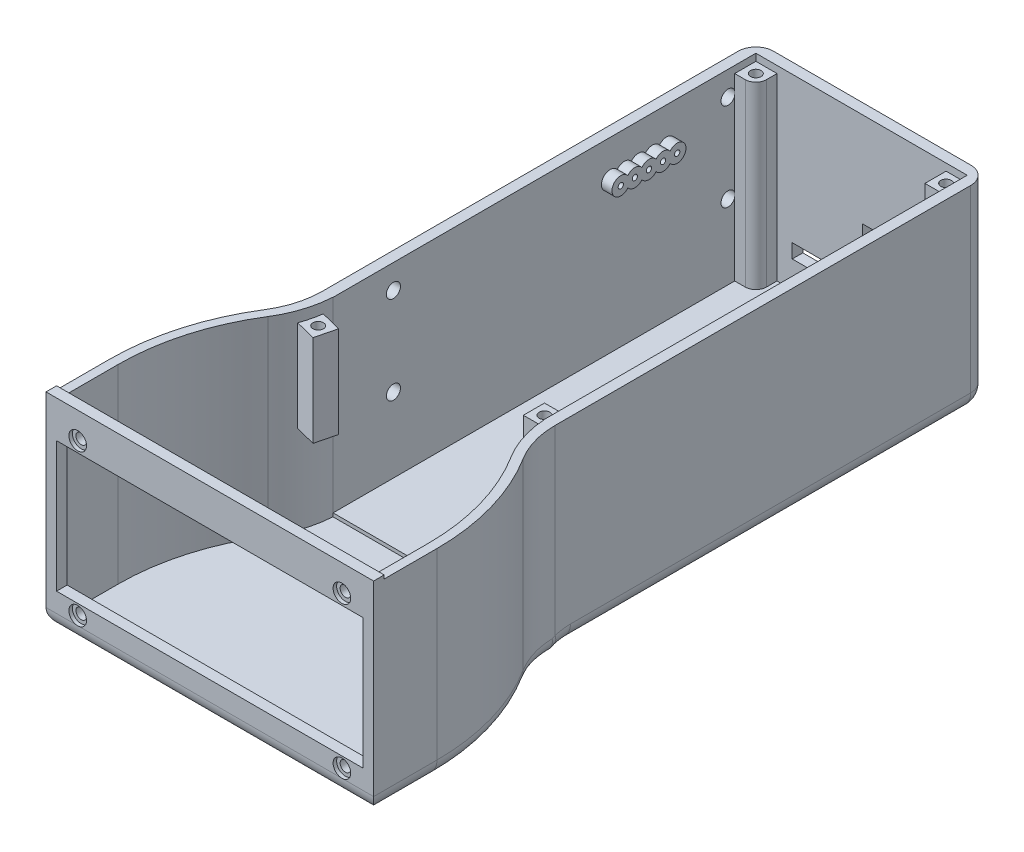
SolidWorks part; units mm, degrees
ref_plane "Front Plane" through (0, 0, 0) normal (0, 0, 1) x (1, 0, 0)
ref_plane "Top Plane" through (0, 0, 0) normal (0, 1, 0) x (1, 0, 0)
ref_plane "Right Plane" through (0, 0, 0) normal (1, 0, 0) x (0, 0, -1)
sketch "Sketch2" plane through (0, 0, -185.0054) normal (0, 0, -1) x (-1, 0, 0)
  line L0 (-30, -25) -> (0, 0) construction
  line L1 (-30, 25) -> (30, 25) construction
  line L2 (-30, 25) -> (-30, -25)
  line L3 (-30, -25) -> (30, -25)
  line L4 (30, 25) -> (30, -25)
  line L5 (0, 0) -> (30, 25) construction
  line L6 (-30, 25) -> (0, 0) construction
  line L7 (0, 0) -> (30, -25) construction
  line L8 (-33, 28) -> (-33, -28)
  line L9 (-33, -28) -> (33, -28)
  line L10 (33, 28) -> (33, -28)
  line L11 (-33, 28) -> (-30, 28)
  line L12 (30, 25) -> (30, 28)
  line L13 (-30, 25) -> (-30, 28)
  line L14 (-30, 28) -> (30, 28) construction
  line L15 (30, 28) -> (33, 28)
  line L16 (-33, 28) -> (33, 28) construction
  dimension "D1" = 60
  dimension "D2" = 50
  dimension "D3" = 3
extrude "Boss-Extrude1" add sketch "Sketch2" against normal blind 120
sketch "Sketch3" plane through (0, -25, 0) normal (0, 1, 0) x (1, 0, 0)
  line L1 (-33, 185.0054) -> (33, 185.0054)
  line L2 (-33, 185.0054) -> (-33, 188.0054)
  line L3 (-33, 188.0054) -> (33, 188.0054)
  line L4 (33, 185.0054) -> (33, 188.0054)
  dimension "D1" = 3
extrude "Boss-Extrude3" add sketch "Sketch3" along normal blind 53 and the other way blind 3
sketch "Sketch4" plane through (0, 0, -188.0054) normal (0, 0, -1) x (-1, 0, 0)
  line L0 (-13.3183, 1.1961) -> (-13.3183, -6.8039)
  line L1 (-12.8183, 0.6961) -> (-0.8183, 0.6961) construction
  line L2 (-12.8183, 0.6961) -> (-12.8183, -6.3039) construction
  line L3 (-12.8183, -6.3039) -> (-0.8183, -6.3039) construction
  line L4 (-0.8183, 0.6961) -> (-0.8183, -6.3039) construction
  line L5 (-13.3183, -6.8039) -> (-0.3183, -6.8039)
  line L6 (-0.3183, 1.1961) -> (-0.3183, -6.8039)
  line L7 (-13.3183, 1.1961) -> (-0.3183, 1.1961)
  line L8 (10.6709, -13.4176) -> (10.6709, -17.4176)
  line L9 (11.1709, -13.9176) -> (19.1709, -13.9176) construction
  line L10 (11.1709, -13.9176) -> (11.1709, -16.9176) construction
  line L11 (11.1709, -16.9176) -> (19.1709, -16.9176) construction
  line L12 (19.1709, -13.9176) -> (19.1709, -16.9176) construction
  line L13 (10.6709, -17.4176) -> (19.6709, -17.4176)
  line L14 (19.6709, -13.4176) -> (19.6709, -17.4176)
  line L15 (10.6709, -13.4176) -> (19.6709, -13.4176)
  line L36 (-12.0343, -12.8639) -> (-2.0343, -20.8639) construction
  line L38 (-12.0343, -19.8639) -> (-2.0343, -19.8639)
  line L39 (-12.0343, -19.8639) -> (-12.0343, -13.8639)
  line L40 (-12.0343, -13.8639) -> (-2.0343, -13.8639)
  line L41 (-2.0343, -19.8639) -> (-2.0343, -13.8639)
  line L42 (-12.0343, -19.8639) -> (-2.0343, -13.8639) construction
  line L43 (-12.0343, -13.8639) -> (-2.0343, -19.8639) construction
  circle A12 centre (1.4657, -16.8639) radius 1.5 construction
  circle A13 centre (-15.5343, -16.8639) radius 1.5 construction
  circle A14 centre (1.4657, -16.8639) radius 1.5
  circle A15 centre (-15.5343, -16.8639) radius 1.5
  arc A16 (-3.0343, -21.8639) -> (-2.0343, -20.8639) centre (-3.0343, -20.8639) ccw construction
  point P31 (-7.0343, -16.8639)
  dimension "D3" = 6
  dimension "D4" = 10
  dimension "D1" = 0.5
  dimension "D2" = 0.5
extrude "Cut-Extrude1" cut sketch "Sketch4" against normal up to next
sketch "Sketch5" plane through (-33, 0, 0) normal (-1, 0, 0) x (0, 0, 1)
  line L0 (-143.2154, 18.1363) -> (-144.1154, 18.1363) construction
  line L1 (-144.1154, 18.1363) -> (-144.1154, 17.0363) construction
  line L2 (-144.1154, 17.0363) -> (-143.2154, 17.0363) construction
  line L3 (-143.2154, 17.0363) -> (-143.2154, 18.1363) construction
  line L4 (-147.2154, 18.1363) -> (-148.1154, 18.1363) construction
  line L5 (-148.1154, 18.1363) -> (-148.1154, 17.0363) construction
  line L6 (-148.1154, 17.0363) -> (-147.2154, 17.0363) construction
  line L7 (-147.2154, 17.0363) -> (-147.2154, 18.1363) construction
  line L8 (-151.2154, 18.1363) -> (-152.1154, 18.1363) construction
  line L9 (-152.1154, 18.1363) -> (-152.1154, 17.0363) construction
  line L10 (-152.1154, 17.0363) -> (-151.2154, 17.0363) construction
  line L11 (-151.2154, 17.0363) -> (-151.2154, 18.1363) construction
  line L12 (-155.2154, 18.1363) -> (-156.1154, 18.1363) construction
  line L13 (-156.1154, 18.1363) -> (-156.1154, 17.0363) construction
  line L14 (-156.1154, 17.0363) -> (-155.2154, 17.0363) construction
  line L15 (-155.2154, 17.0363) -> (-155.2154, 18.1363) construction
  line L16 (-160.1154, 17.0363) -> (-159.2154, 17.0363) construction
  line L17 (-159.2154, 17.0363) -> (-159.2154, 18.1363) construction
  line L18 (-159.2154, 18.1363) -> (-160.1154, 18.1363) construction
  line L19 (-160.1154, 18.1363) -> (-160.1154, 17.0363) construction
  line L20 (-143.2154, 18.1363) -> (-144.1154, 18.1363) construction
  line L21 (-144.1154, 18.1363) -> (-144.1154, 17.0363) construction
  line L22 (-144.1154, 17.0363) -> (-143.2154, 17.0363) construction
  line L23 (-143.2154, 17.0363) -> (-143.2154, 18.1363) construction
  line L24 (-147.2154, 18.1363) -> (-148.1154, 18.1363) construction
  line L25 (-148.1154, 18.1363) -> (-148.1154, 17.0363) construction
  line L26 (-148.1154, 17.0363) -> (-147.2154, 17.0363) construction
  line L27 (-147.2154, 17.0363) -> (-147.2154, 18.1363) construction
  line L28 (-151.2154, 18.1363) -> (-152.1154, 18.1363) construction
  line L29 (-152.1154, 18.1363) -> (-152.1154, 17.0363) construction
  line L30 (-152.1154, 17.0363) -> (-151.2154, 17.0363) construction
  line L31 (-151.2154, 17.0363) -> (-151.2154, 18.1363) construction
  line L32 (-155.2154, 18.1363) -> (-156.1154, 18.1363) construction
  line L33 (-156.1154, 18.1363) -> (-156.1154, 17.0363) construction
  line L34 (-156.1154, 17.0363) -> (-155.2154, 17.0363) construction
  line L35 (-155.2154, 17.0363) -> (-155.2154, 18.1363) construction
  line L36 (-160.1154, 17.0363) -> (-159.2154, 17.0363) construction
  line L37 (-159.2154, 17.0363) -> (-159.2154, 18.1363) construction
  line L38 (-159.2154, 18.1363) -> (-160.1154, 18.1363) construction
  line L39 (-160.1154, 18.1363) -> (-160.1154, 17.0363) construction
  line L40 (-160.1154, 17.0363) -> (-159.2154, 18.1363) construction
  line L41 (-156.1154, 17.0363) -> (-155.2154, 18.1363) construction
  line L42 (-152.1154, 17.0363) -> (-151.2154, 18.1363) construction
  line L43 (-148.1154, 18.1363) -> (-147.2154, 17.0363) construction
  line L44 (-144.1154, 17.0363) -> (-143.2154, 18.1363) construction
  circle A0 centre (-82.1154, 21.1363) radius 1.5 construction
  circle A1 centre (-82.1154, -3.8637) radius 1.5 construction
  circle A2 centre (-177.1154, 21.1363) radius 1.5 construction
  circle A3 centre (-177.1154, -3.8637) radius 1.5 construction
  circle A4 centre (-82.1154, 21.1363) radius 1.5 construction
  circle A5 centre (-82.1154, -3.8637) radius 1.5 construction
  circle A6 centre (-177.1154, 21.1363) radius 1.5 construction
  circle A7 centre (-177.1154, -3.8637) radius 1.5 construction
  circle A8 centre (-177.1154, 21.1363) radius 2
  circle A9 centre (-177.1154, -3.8637) radius 2
  circle A10 centre (-82.1154, -3.8637) radius 2
  circle A11 centre (-82.1154, 21.1363) radius 2
  circle A12 centre (-159.6654, 17.5863) radius 0.75
  circle A13 centre (-155.6654, 17.5863) radius 0.75
  circle A14 centre (-151.6654, 17.5863) radius 0.75
  circle A15 centre (-147.6654, 17.5863) radius 0.75
  circle A16 centre (-143.6654, 17.5863) radius 0.75
  dimension "D1" = 0.5
  dimension "D2" = 1.5
  dimension "D3" = 1.5
  dimension "D4" = 1.5
  dimension "D5" = 1.5
  dimension "D6" = 1.5
extrude "Cut-Extrude2" cut sketch "Sketch5" against normal up to next
sketch "Sketch6" plane through (-33, 0, 0) normal (-1, 0, 0) x (0, 0, 1)
  arc A0 (-157.6654, 19.0863) -> (-157.6654, 16.0863) centre (-159.6654, 17.5863) ccw
  arc A1 (-157.6654, 16.0863) -> (-153.6654, 16.0863) centre (-155.6654, 17.5863) ccw
  arc A2 (-153.6654, 16.0863) -> (-149.6654, 16.0863) centre (-151.6654, 17.5863) ccw
  arc A3 (-149.6654, 16.0863) -> (-145.6654, 16.0863) centre (-147.6654, 17.5863) ccw
  arc A4 (-145.6654, 16.0863) -> (-145.6654, 19.0863) centre (-143.6654, 17.5863) ccw
  circle A5 centre (-159.6654, 17.5863) radius 0.75 construction
  circle A6 centre (-155.6654, 17.5863) radius 0.75 construction
  circle A7 centre (-151.6654, 17.5863) radius 0.75 construction
  circle A8 centre (-147.6654, 17.5863) radius 0.75 construction
  circle A9 centre (-143.6654, 17.5863) radius 0.75 construction
  circle A10 centre (-159.6654, 17.5863) radius 0.75
  circle A11 centre (-155.6654, 17.5863) radius 0.75
  circle A12 centre (-151.6654, 17.5863) radius 0.75
  circle A13 centre (-147.6654, 17.5863) radius 0.75
  circle A14 centre (-143.6654, 17.5863) radius 0.75
  arc A15 (-157.6654, 19.0863) -> (-157.6654, 16.0863) centre (-155.6654, 17.5863) ccw construction
  arc A16 (-157.6654, 16.0863) -> (-157.6654, 19.0863) centre (-159.6654, 17.5863) ccw construction
  arc A17 (-153.6654, 19.0863) -> (-153.6654, 16.0863) centre (-151.6654, 17.5863) ccw construction
  arc A18 (-153.6654, 16.0863) -> (-153.6654, 19.0863) centre (-155.6654, 17.5863) ccw construction
  arc A19 (-153.6654, 19.0863) -> (-157.6654, 19.0863) centre (-155.6654, 17.5863) ccw
  arc A20 (-149.6654, 19.0863) -> (-149.6654, 16.0863) centre (-147.6654, 17.5863) ccw construction
  arc A21 (-149.6654, 16.0863) -> (-149.6654, 19.0863) centre (-151.6654, 17.5863) ccw construction
  arc A22 (-149.6654, 19.0863) -> (-153.6654, 19.0863) centre (-151.6654, 17.5863) ccw
  arc A23 (-145.6654, 19.0863) -> (-145.6654, 16.0863) centre (-143.6654, 17.5863) ccw construction
  arc A24 (-145.6654, 16.0863) -> (-145.6654, 19.0863) centre (-147.6654, 17.5863) ccw construction
  arc A25 (-145.6654, 19.0863) -> (-149.6654, 19.0863) centre (-147.6654, 17.5863) ccw
  dimension "D1" = 5
  dimension "D2" = 5
  dimension "D3" = 5
  dimension "D4" = 5
  dimension "D5" = 5
extrude "Boss-Extrude4" add sketch "Sketch6" against normal blind 3 from surface starting at face at (-30, -3.8637, -179.1154)
sketch "Sketch7" plane through (0, 0, 0) normal (0, 0, 1) x (1, 0, 0)
  line L0 (-43, -18) -> (43, -18) construction
  line L1 (43, -18) -> (43, 18) construction
  line L2 (-43, 18) -> (43, 18) construction
  line L3 (-43, -18) -> (-43, 18) construction
  line L4 (-43, -18) -> (43, -18) construction
  line L5 (43, -18) -> (43, 18) construction
  line L6 (-43, 18) -> (43, 18) construction
  line L7 (-43, -18) -> (-43, 18) construction
  line L8 (-43.5, -18.5) -> (-43.5, 18.5)
  line L9 (-43.5, 18.5) -> (43.5, 18.5)
  line L10 (43.5, -18.5) -> (43.5, 18.5)
  line L11 (-43.5, -18.5) -> (43.5, -18.5)
  line L13 (46.5, -29) -> (-46.5, -29)
  line L14 (46.5, -29) -> (46.5, 29)
  line L15 (46.5, 29) -> (-46.5, 29)
  line L16 (-46.5, -29) -> (-46.5, 29)
  line L17 (46.5, -29) -> (-46.5, 29) construction
  line L18 (46.5, 29) -> (-46.5, -29) construction
  circle A0 centre (37.5, 21.5) radius 1.5 construction
  circle A1 centre (37.5, -21.5) radius 1.5 construction
  circle A2 centre (-37.5, -21.5) radius 1.5 construction
  circle A3 centre (-37.5, 21.5) radius 1.5 construction
  circle A4 centre (37.5, 21.5) radius 1.5
  circle A5 centre (37.5, -21.5) radius 1.5
  circle A6 centre (-37.5, -21.5) radius 1.5
  circle A7 centre (-37.5, 21.5) radius 1.5
  point P20 (0, 0)
  dimension "D2" = 3
  dimension "D3" = 7.5
  dimension "D1" = 0.5
extrude "Boss-Extrude5" add sketch "Sketch7" against normal blind 3 separate body
sketch "Sketch8" plane through (0, 0, 0) normal (0, 0, 1) x (1, 0, 0)
  circle A11 centre (-37.5, 21.5) radius 2.5
  circle A12 centre (37.5, 21.5) radius 2.5
  circle A13 centre (37.5, -21.5) radius 2.5
  circle A14 centre (-37.5, -21.5) radius 2.5
  point P0 (37.5, 21.5)
  point P1 (37.5, -21.5)
  point P2 (-37.5, -21.5)
  point P22 (-37.5, 21.5)
  dimension "D1" = 5
  dimension "D2" = 5
  dimension "D3" = 5
  dimension "D4" = 5
extrude "Cut-Extrude3" cut sketch "Sketch8" against normal blind 1
sketch "Sketch15" plane through (0, -28, 0) normal (0, -1, 0) x (1, 0, 0)
  line L0 (46.5, -3) -> (-46.5, -3)
  line L1 (44, -3) -> (44, -18)
  line L2 (33, -65.0054) -> (-33, -65.0054)
  line L3 (46.5, -3) -> (46.5, -18)
  line L4 (30, -65.0054) -> (30, -185.0054) construction
  line L5 (33, -65.0054) -> (33, -188.0054) construction
  line L6 (-30, -65.0054) -> (30, -65.0054) construction
  arc A0 (30.0511, -65.0054) -> (34.5208, -51.0054) centre (59.6645, -66.7464) cw
  arc A1 (34.5208, -51.0054) -> (44, -18) centre (-18.2002, -18) ccw
  arc A2 (36.6398, -52.332) -> (46.5, -18) centre (-18.2002, -18) ccw
  arc A3 (36.6398, -52.332) -> (33, -65.0054) centre (56.8836, -65.0054) ccw
  arc A4 (32.5468, -65.1522) -> (36.6398, -52.332) centre (59.6645, -66.7464) cw construction
  line M11 (33, -65.0054) -> (-33, -65.0054)
  dimension "D1" = 2.5
  dimension "D2" = 15
  dimension "D3" = 2.5
  dimension "D4" = 14
extrude "Boss-Extrude6" add sketch "Sketch15" against normal blind 56 contours A3 A2 L3 L0 L1 A1 A0 M11 region at (45.8585, -28, -10.5)
mirror "Mirror2" about plane through (0, 0, 0) normal (1, 0, 0) of "Boss-Extrude6"
sketch "Sketch17" plane through (0, -29, 0) normal (0, -1, 0) x (1, 0, 0)
  line L0 (46.5, -3) -> (46.5, -18) construction
  line L1 (-46.5, -3) -> (-46.5, -18) construction
  line L2 (46.5, -3) -> (46.5, -18)
  line L3 (-46.5, -3) -> (-46.5, -18)
  line L4 (-46.5, -3) -> (46.5, -3)
  line L5 (33, -65.0054) -> (-33, -65.0054)
  arc A0 (36.6398, -52.332) -> (46.5, -18) centre (-18.2002, -18) ccw construction
  arc A1 (36.6398, -52.332) -> (33, -65.0054) centre (56.8836, -65.0054) ccw construction
  arc A2 (-33, -65.0054) -> (-36.6398, -52.332) centre (-56.8836, -65.0054) ccw construction
  arc A3 (-46.5, -18) -> (-36.6398, -52.332) centre (18.2002, -18) ccw construction
  arc A4 (36.6398, -52.332) -> (46.5, -18) centre (-18.2002, -18) ccw
  arc A5 (36.6398, -52.332) -> (33, -65.0054) centre (56.8836, -65.0054) ccw
  arc A6 (-33, -65.0054) -> (-36.6398, -52.332) centre (-56.8836, -65.0054) ccw
  arc A7 (-46.5, -18) -> (-36.6398, -52.332) centre (18.2002, -18) ccw
extrude "Boss-Extrude8" add sketch "Sketch17" against normal blind 3
fillet "Fillet1" radius 10 1 edges at (0, -28, -65.0054)
fillet "Fillet2" radius 5 14 edges at (-33.928, -29, -58.4126) (-43.9861, -29, -35.8599) (46.5, -29, -9) (43.9861, -29, -35.8599) (33, -28.2532, -67.1283) (-33, -28.2532, -67.1283) (-46.5, -29, -9) (0, -29, 0) (33.928, -29, -58.4126) (33, -28, -128.6849) (0, -28, -188.0054) (-33, -28, -128.6849) (33, 0, -188.0054) (-33, 0, -188.0054)
sketch "Sketch18" plane through (0, -25, 0) normal (0, 1, 0) x (1, 0, 0)
  line L0 (-30, 185.0054) -> (30, 185.0054) construction
  line L1 (24, 185.0054) -> (30, 185.0054)
  line L2 (24, 185.0054) -> (24, 179.0054)
  line L3 (24, 179.0054) -> (30, 179.0054)
  line L4 (30, 185.0054) -> (30, 179.0054)
  line L5 (30, 65.0054) -> (30, 185.0054) construction
  line L6 (0, -32.0535) -> (0, 32.0535) construction
  line L7 (-27, 179.0054) -> (-30, 179.0054)
  line L8 (-30, 185.0054) -> (-30, 179.0054)
  line L9 (-24, 185.0054) -> (-30, 185.0054)
  line L10 (-24, 185.0054) -> (-24, 182.0054)
  line L11 (24, 71.0054) -> (30, 65.0054) construction
  line L12 (30, 65.0054) -> (24, 65.0054)
  line L13 (30, 65.0054) -> (30, 71.0054)
  line L14 (30, 71.0054) -> (24, 71.0054)
  line L15 (24, 65.0054) -> (24, 71.0054)
  circle A0 centre (27, 182.0054) radius 1.5
  circle A1 centre (-27, 182.0054) radius 1.5
  arc A2 (-27, 179.0054) -> (-24, 182.0054) centre (-27, 182.0054) ccw
  circle A3 centre (27, 68.0054) radius 1.5
  point P20 (-24, 179.0054)
  dimension "D1" = 3
  dimension "D5" = 3
  dimension "D6" = 3
  dimension "D9" = 3
  dimension "D2" = 6
  dimension "D3" = 6
  dimension "D4" = 3
  dimension "D7" = 6
  dimension "D8" = 6
extrude "Boss-Extrude9" add sketch "Sketch18" along normal blind 51
sketch "Sketch20" plane through (0, -26, 0) normal (0, 1, 0) x (1, 0, 0)
  line L0 (-30.303, 62.5176) -> (-31.7545, 56.6958) construction
  line L1 (-30.303, 62.5176) -> (-24.4812, 61.066)
  line L2 (-31.7545, 56.6958) -> (-25.9327, 55.2443)
  line L3 (-24.4812, 61.066) -> (-25.9327, 55.2443)
  line L4 (-30.0511, 65.0054) -> (30.0511, 65.0054) construction
  line L5 (-30.303, 62.5176) -> (-25.9327, 55.2443) construction
  arc A0 (-34.5208, 51.0054) -> (-30.0511, 65.0054) centre (-59.6645, 66.7464) ccw construction
  arc A1 (-31.7545, 56.6958) -> (-30.303, 62.5176) centre (-59.6645, 66.7464) ccw
  circle A2 centre (-28.1178, 58.8809) radius 1.5
  arc A3 (-34.5208, 51.0054) -> (-31.7545, 56.6958) centre (-59.6645, 66.7464) ccw construction
  arc A4 (-30.303, 62.5176) -> (-30.0511, 65.0054) centre (-59.6645, 66.7464) ccw construction
  dimension "D4" = 3
  dimension "D1" = 6
  dimension "D2" = 14
  dimension "D3" = 6
extrude "Boss-Extrude10" add sketch "Sketch20" along normal blind 26 from offset 25
